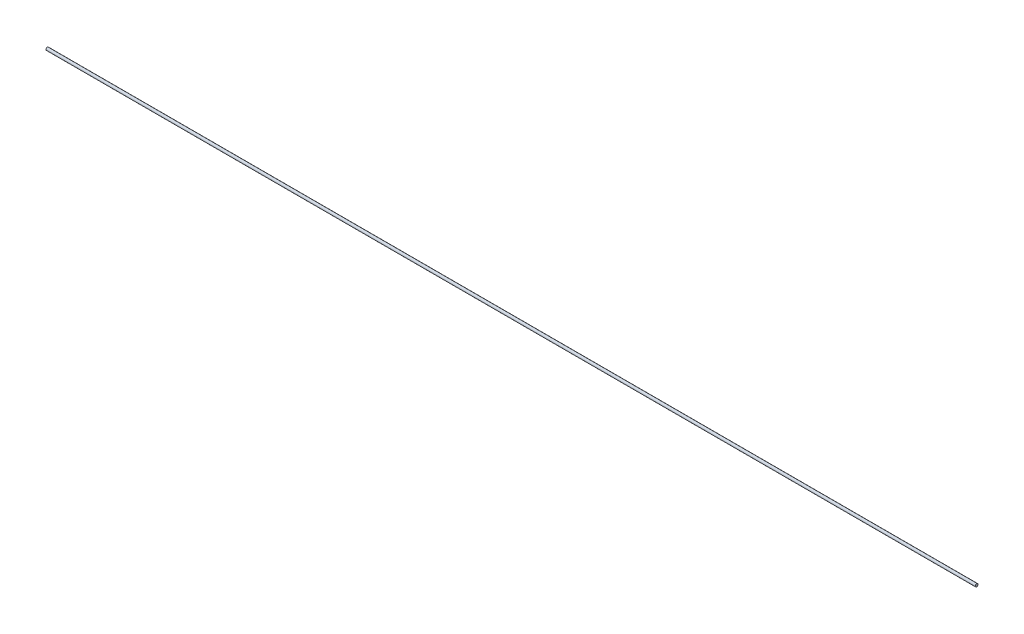
SolidWorks part; units mm, degrees
ref_plane "Front Plane" through (0, 0, 0) normal (0, 0, 1) x (1, 0, 0)
ref_plane "Top Plane" through (0, 0, 0) normal (0, 1, 0) x (1, 0, 0)
ref_plane "Right Plane" through (0, 0, 0) normal (1, 0, 0) x (0, 0, -1)
sketch "Cable Sketch" plane through (0, 0, 0) normal (0, 0, 1) x (1, 0, 0)
  line L0 (-3000, 0) -> (3000, 0) construction
  line L1 (12, 0) -> (809.2481, 0)
  line L2 (809.2481, 0) -> (809.2481, 1.19)
  line L3 (809.2481, 1.19) -> (12, 1.19)
  line L4 (12, 1.19) -> (12, 0)
revolve "Cable" add sketch "Cable Sketch" angle 360 about L0
ref_axis "Engine Axis" through (862.3105, 0, 0) along (-1, 0, 0)
sketch "End Points" plane through (0, 0, 0) normal (0, 0, 1) x (1, 0, 0)
  point P0 (0, 0)
  point P1 (821.2481, 0)
